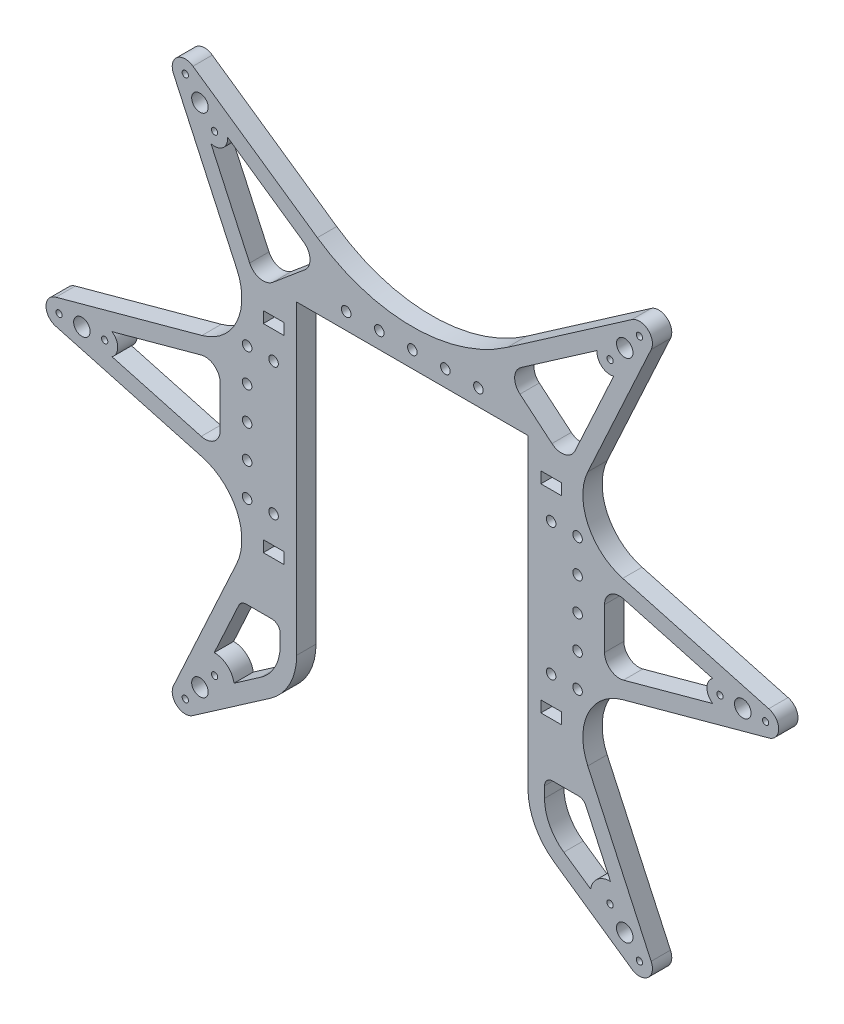
SolidWorks part; units mm, degrees
material "Acrylic (Medium-high impact)"
ref_plane "Front Plane" through (0, 0, 0) normal (0, 0, 1) x (1, 0, 0)
ref_plane "Top Plane" through (0, 0, 0) normal (0, 1, 0) x (1, 0, 0)
ref_plane "Right Plane" through (0, 0, 0) normal (1, 0, 0) x (0, 0, -1)
sketch "Sketch1" plane through (0, 0, 0) normal (0, 0, 1) x (1, 0, 0)
  line L0 (587.1768, 489.0962) -> (587.1768, 412.0041) construction
  line L1 (549.3782, 453.8298) -> (576.3894, 461.205)
  line L2 (601.3767, 418.8158) -> (595.1767, 422.2158) construction
  line L3 (590.0159, 402.7396) -> (597.7767, 402.7396)
  line L4 (600.2767, 396.9582) -> (600.2767, 400.2396)
  line L5 (601.3767, 422.2158) -> (595.1767, 418.8158) construction
  line L6 (532.4267, 446.7161) -> (532.4267, 450.5502) construction
  line L7 (576.6167, 434.6502) -> (532.4267, 446.7161)
  line L8 (635.7171, 455.9841) -> (-31503.6634, 38758.2062) construction
  line L9 (532.4267, 450.5502) -> (532.4267, 454.3842) construction
  line L10 (601.3767, 422.2158) -> (601.3767, 418.8158)
  line L11 (601.3767, 422.2158) -> (595.1767, 422.2158)
  line L12 (595.1767, 422.2158) -> (595.1767, 418.8158)
  line L13 (549.3782, 447.2706) -> (576.3894, 439.8953)
  line L14 (575.9979, 527.1546) -> (571.5627, 532.4403) construction
  line L15 (575.9979, 527.1546) -> (580.4331, 521.8689) construction
  line L16 (601.3767, 418.8158) -> (595.1767, 418.8158)
  line L17 (576.6167, 466.4501) -> (576.6167, 434.6502) construction
  line L18 (694.2433, 380.1612) -> (686.125, 385.7883)
  line L19 (570.952, 533.1681) -> (573.8891, 535.6326) construction
  line L20 (-358.0106, 400.5502) -> (49641.9894, 400.5502) construction
  line L21 (540.2767, 450.5502) -> (547.1767, 450.5502) construction
  line L22 (-351.1587, 450.5502) -> (49648.8413, 450.5502) construction
  line L23 (680.2767, 396.9582) -> (680.2767, 400.2396)
  line L24 (582.1207, 456.8289) -> (582.1207, 444.2715)
  line L25 (685.3767, 482.2502) -> (679.1767, 478.8502) construction
  line L26 (587.1768, 489.0962) -> (568.0149, 530.7036)
  line L27 (690.5374, 402.7396) -> (682.7767, 402.7396)
  line L28 (700.2251, 385.1805) -> (692.8082, 401.2854)
  line L29 (685.3767, 478.8502) -> (679.1767, 482.2502) construction
  line L30 (611.5369, 509.5368) -> (573.8891, 535.6326)
  line L31 (568.0149, 530.7036) -> (570.952, 533.1681) construction
  line L32 (610.8062, 450.5502) -> (605.2767, 450.5502) construction
  line L33 (605.2767, 489.5502) -> (675.2767, 489.5502)
  line L34 (663.4579, 478.1765) -> (-31475.9226, -37824.0456) construction
  line L35 (540.2767, 450.5502) -> (533.3767, 450.5502) construction
  line L36 (576.6167, 466.4501) -> (532.4267, 454.3842)
  line L37 (575.9979, 373.9457) -> (571.5627, 368.66) construction
  line L38 (683.2767, 381.679) -> (706.6642, 365.4678)
  line L39 (709.6013, 367.9323) -> (712.5384, 370.3968) construction
  line L40 (580.3282, 385.1805) -> (587.7451, 401.2854)
  line L41 (640.2767, 450.5502) -> (675.2767, 450.5502) construction
  line L42 (706.6642, 365.4678) -> (709.6013, 367.9323) construction
  line L43 (704.5554, 373.9457) -> (700.1202, 379.2314) construction
  line L44 (704.5554, 373.9457) -> (708.9906, 368.66) construction
  line L45 (740.2767, 450.5502) -> (747.1767, 450.5502) construction
  line L46 (586.31, 380.1612) -> (594.4283, 385.7883)
  line L47 (669.7471, 450.5502) -> (675.2767, 450.5502) construction
  line L48 (575.9979, 373.9457) -> (580.4331, 379.2314) construction
  line L49 (587.1768, 412.0041) -> (568.0149, 370.3968)
  line L50 (712.5384, 530.7036) -> (709.6013, 533.1681) construction
  line L51 (740.2767, 450.5502) -> (733.3767, 450.5502) construction
  line L52 (573.8891, 365.4678) -> (570.952, 367.9323) construction
  line L53 (570.952, 367.9323) -> (568.0149, 370.3968) construction
  line L54 (709.6013, 533.1681) -> (706.6642, 535.6326) construction
  line L55 (597.2767, 381.679) -> (573.8891, 365.4678)
  line L56 (703.9366, 466.4501) -> (703.9366, 434.6502) construction
  line L58 (704.5554, 527.1546) -> (700.1202, 521.8689) construction
  line L59 (704.5554, 527.1546) -> (708.9906, 532.4403) construction
  line L60 (748.1267, 450.5502) -> (748.1267, 454.3842) construction
  line L61 (748.1267, 446.7161) -> (748.1267, 450.5502) construction
  line L62 (1630.6528, 450.5502) -> (-48369.3472, 450.5502) construction
  line L63 (691.7267, 450.5502) -> (588.8267, 450.5502) construction
  line L64 (679.1767, 422.2158) -> (685.3767, 418.8158) construction
  line L67 (693.3765, 489.0962) -> (693.3765, 412.0041) construction
  line L68 (-358.708, 500.5502) -> (49641.292, 500.5502) construction
  line L69 (579.336, 518.0744) -> (591.0486, 492.6418)
  line L70 (679.1767, 418.8158) -> (685.3767, 422.2158) construction
  line L71 (685.3767, 478.8502) -> (685.3767, 482.2502)
  line L72 (605.2767, 489.5502) -> (605.2767, 396.9582)
  line L73 (584.3606, 522.2905) -> (607.3728, 506.3395)
  line L74 (607.7017, 499.196) -> (598.0264, 491.0775)
  line L75 (685.3767, 478.8502) -> (679.1767, 478.8502)
  line L76 (679.1767, 478.8502) -> (679.1767, 482.2502)
  line L77 (672.8516, 499.196) -> (682.5269, 491.0775)
  line L78 (696.1927, 522.2905) -> (673.1805, 506.3395)
  line L79 (675.2767, 489.5502) -> (675.2767, 396.9582)
  line L81 (701.2173, 518.0744) -> (689.5047, 492.6418)
  line L83 (693.3765, 412.0041) -> (712.5384, 370.3968)
  line L87 (703.9366, 466.4501) -> (748.1267, 454.3842)
  line L88 (669.0164, 509.5368) -> (706.6642, 535.6326)
  line L89 (693.3765, 489.0962) -> (712.5384, 530.7036)
  line L90 (698.4326, 456.8289) -> (698.4326, 444.2715)
  line L91 (685.3767, 482.2502) -> (679.1767, 482.2502)
  line L92 (731.1751, 447.2706) -> (704.1639, 439.8953)
  line L93 (679.1767, 418.8158) -> (685.3767, 418.8158)
  line L94 (685.3767, 422.2158) -> (685.3767, 418.8158)
  line L95 (679.1767, 422.2158) -> (685.3767, 422.2158)
  line L96 (703.9366, 434.6502) -> (748.1267, 446.7161)
  line L97 (731.1751, 453.8298) -> (704.1639, 461.205)
  line L98 (679.1767, 422.2158) -> (679.1767, 418.8158)
  line L100 (590.2767, 450.5502) -> (590.2767, 460.5502) construction
  line L102 (640.2767, 494.5502) -> (630.2767, 494.5502) construction
  line L104 (568.9811, 521.2669) -> (581.557, 531.8192) construction
  line L111 (640.2767, -500.116) -> (640.2767, 49499.884) construction
  line L157 (595.1767, 482.2502) -> (601.3767, 482.2502)
  line L158 (601.3767, 478.8502) -> (601.3767, 482.2502)
  line L159 (595.1767, 478.8502) -> (601.3767, 482.2502) construction
  line L162 (595.1767, 482.2502) -> (601.3767, 478.8502) construction
  line L163 (595.1767, 478.8502) -> (601.3767, 478.8502)
  line L164 (595.1767, 478.8502) -> (595.1767, 482.2502)
  circle A0 centre (533.3767, 450.5502) radius 0.95
  arc A1 (582.1207, 444.2715) -> (576.3894, 439.8953) centre (577.5843, 444.2715) cw
  circle A2 centre (575.9979, 527.1546) radius 2.5
  circle A3 centre (547.1767, 450.5502) radius 0.95
  arc A4 (549.3782, 447.2706) -> (549.3782, 453.8298) centre (547.1767, 450.5502) ccw
  circle A5 centre (540.2767, 450.5502) radius 2.5
  arc A6 (532.4267, 446.7161) -> (532.4267, 454.3842) centre (533.3767, 450.5502) cw
  circle A7 centre (590.2767, 460.5502) radius 1.45
  circle A8 centre (571.5627, 532.4403) radius 0.95
  circle A9 centre (580.4331, 521.8689) radius 0.95
  arc A10 (579.336, 518.0744) -> (584.3606, 522.2905) centre (580.4331, 521.8689) ccw
  arc A11 (582.1207, 456.8289) -> (576.3894, 461.205) centre (577.5843, 456.8289) ccw
  arc A12 (600.2767, 400.2396) -> (597.7767, 402.7396) centre (597.7767, 400.2396) ccw
  circle A13 centre (682.2767, 470.5502) radius 1.45
  arc A14 (586.31, 380.1612) -> (580.3282, 385.1805) centre (580.4331, 379.2314) ccw
  arc A15 (568.0149, 530.7036) -> (573.8891, 535.6326) centre (571.5627, 532.4403) cw
  arc A16 (605.2767, 396.9582) -> (597.2767, 381.679) centre (586.6858, 396.9582) cw
  arc A17 (600.2767, 396.9582) -> (594.4283, 385.7883) centre (586.6858, 396.9582) cw
  arc A18 (587.7451, 401.2854) -> (590.0159, 402.7396) centre (590.0159, 400.2396) cw
  arc A19 (675.2767, 396.9582) -> (683.2767, 381.679) centre (693.8675, 396.9582) ccw
  circle A20 centre (630.2767, 494.5502) radius 1.45
  circle A21 centre (620.2767, 494.5502) radius 1.45
  arc A22 (680.2767, 396.9582) -> (686.125, 385.7883) centre (693.8675, 396.9582) ccw
  arc A23 (680.2767, 400.2396) -> (682.7767, 402.7396) centre (682.7767, 400.2396) cw
  arc A24 (692.8082, 401.2854) -> (690.5374, 402.7396) centre (690.5374, 400.2396) ccw
  arc A25 (694.2433, 380.1612) -> (700.2251, 385.1805) centre (700.1202, 379.2314) cw
  circle A27 centre (580.4331, 379.2314) radius 0.95
  circle A28 centre (575.9979, 373.9457) radius 2.5
  circle A29 centre (571.5627, 368.66) radius 0.95
  arc A30 (573.8891, 365.4678) -> (568.0149, 370.3968) centre (571.5627, 368.66) cw
  arc A31 (611.5369, 509.5368) -> (669.0164, 509.5368) centre (640.2767, 550.9991) ccw
  arc A35 (576.6167, 434.6502) -> (587.1768, 412.0041) centre (572.3036, 418.8538) cw
  arc A36 (598.0264, 491.0775) -> (591.0486, 492.6418) centre (595.1348, 494.5236) cw
  arc A37 (607.7017, 499.196) -> (607.3728, 506.3395) centre (604.8101, 502.6422) ccw
  arc A38 (576.6167, 466.4501) -> (587.1768, 489.0962) centre (572.3036, 482.2466) ccw
  circle A40 centre (590.2767, 430.5502) radius 1.45
  circle A42 centre (590.2767, 440.5502) radius 1.45
  arc A44 (703.9366, 466.4501) -> (693.3765, 489.0962) centre (708.2497, 482.2466) cw
  arc A45 (672.8516, 499.196) -> (673.1805, 506.3395) centre (675.7432, 502.6422) cw
  arc A46 (682.5269, 491.0775) -> (689.5047, 492.6418) centre (685.4185, 494.5236) ccw
  arc A47 (703.9366, 434.6502) -> (693.3765, 412.0041) centre (708.2497, 418.8538) ccw
  circle A49 centre (590.2767, 470.5502) radius 1.45
  circle A50 centre (682.2767, 430.5502) radius 1.45
  arc A51 (706.6642, 365.4678) -> (712.5384, 370.3968) centre (708.9906, 368.66) ccw
  circle A52 centre (708.9906, 368.66) radius 0.95
  circle A53 centre (704.5554, 373.9457) radius 2.5
  circle A54 centre (700.1202, 379.2314) radius 0.95
  circle A58 centre (660.2767, 494.5502) radius 1.45
  circle A59 centre (650.2767, 494.5502) radius 1.45
  arc A63 (712.5384, 530.7036) -> (706.6642, 535.6326) centre (708.9906, 532.4403) ccw
  arc A66 (698.4326, 456.8289) -> (704.1639, 461.205) centre (702.969, 456.8289) cw
  arc A67 (701.2173, 518.0744) -> (696.1927, 522.2905) centre (700.1202, 521.8689) cw
  circle A68 centre (700.1202, 521.8689) radius 0.95
  circle A69 centre (708.9906, 532.4403) radius 0.95
  circle A70 centre (690.2767, 450.5502) radius 1.45
  arc A71 (748.1267, 446.7161) -> (748.1267, 454.3842) centre (747.1767, 450.5502) ccw
  circle A72 centre (740.2767, 450.5502) radius 2.5
  arc A74 (731.1751, 447.2706) -> (731.1751, 453.8298) centre (733.3767, 450.5502) cw
  circle A75 centre (733.3767, 450.5502) radius 0.95
  circle A76 centre (704.5554, 527.1546) radius 2.5
  arc A77 (698.4326, 444.2715) -> (704.1639, 439.8953) centre (702.969, 444.2715) ccw
  circle A78 centre (747.1767, 450.5502) radius 0.95
  circle A81 centre (690.2767, 470.5502) radius 1.45
  circle A82 centre (640.2767, 494.5502) radius 1.45
  circle A83 centre (690.2767, 440.5502) radius 1.45
  circle A84 centre (690.2767, 430.5502) radius 1.45
  circle A86 centre (690.2767, 460.5502) radius 1.45
  circle A89 centre (590.2767, 450.5502) radius 1.45
  circle A92 centre (598.2767, 430.5502) radius 1.45
  circle A129 centre (598.2767, 470.5502) radius 1.45
  circle A130 centre (590.2767, 480.5502) radius 1.45 [skipped]
  point P0 (640.2767, 500.5502)
  point P1 (640.2767, 400.5502)
  point P23 (599.5444, 402.0074)
  point P25 (598.2767, 420.5158)
  point P46 (582.1207, 450.5502)
  point P48 (584.2577, 383.7894)
  point P54 (602.8641, 495.1368)
  point P55 (582.9721, 518.843)
  point P64 (582.1207, 450.5502)
  point P104 (640.2767, 489.5502)
  point P124 (602.8641, 495.1368)
  point P157 (696.2956, 383.7894)
  point P229 (677.6892, 495.1368)
  point P231 (698.4326, 450.5502)
  point P238 (640.2767, 489.5502)
  point P242 (569.0236, 535.4662)
  point P307 (640.2767, 500.5502)
  point P366 (598.2767, 480.5502)
  dimension "D6" = 1.9
  dimension "D9" = 42
  dimension "D7" = 2.9
  dimension "D11" = 5
  dimension "D12" = 13.8
  dimension "D5" = 50
  dimension "D14" = 20
  dimension "D15" = 50
  dimension "D16" = 4
  dimension "D17" = 3
  dimension "D18" = 5
  dimension "D19" = 75
  dimension "D20" = 2.9
  dimension "D13" = 70
  dimension "D27" = 28
  dimension "D8" = 1.9
  dimension "D36" = 3
  dimension "D37" = 3
  dimension "D29" = 1.9
  dimension "D47" = 5
  dimension "D28" = 3
  dimension "D25" = 3
  dimension "D38" = 3
  dimension "D39" = 5
  dimension "D26" = 2.5
  dimension "D52" = 5
  dimension "D50" = 5
  dimension "D51" = 39
  dimension "D10" = 10
  dimension "D21" = 44
  dimension "D22" = 13.8
  dimension "D23" = 8
  dimension "D24" = 5
  dimension "D30" = 13.8
  dimension "D31" = 75
  dimension "D32" = 100
  dimension "D33" = 50
  dimension "D34" = 6.2
  dimension "D35" = 100
  dimension "D40" = 100
  dimension "D41" = 5
  dimension "D42" = 5
  dimension "D43" = 100
  dimension "D44" = 3.4
  dimension "D53" = 10
  dimension "D56" = 10
  dimension "D59" = 5
  dimension "D61" = 28
extrude "Boss-Extrude1" add sketch "Sketch1" along normal blind 5.85
